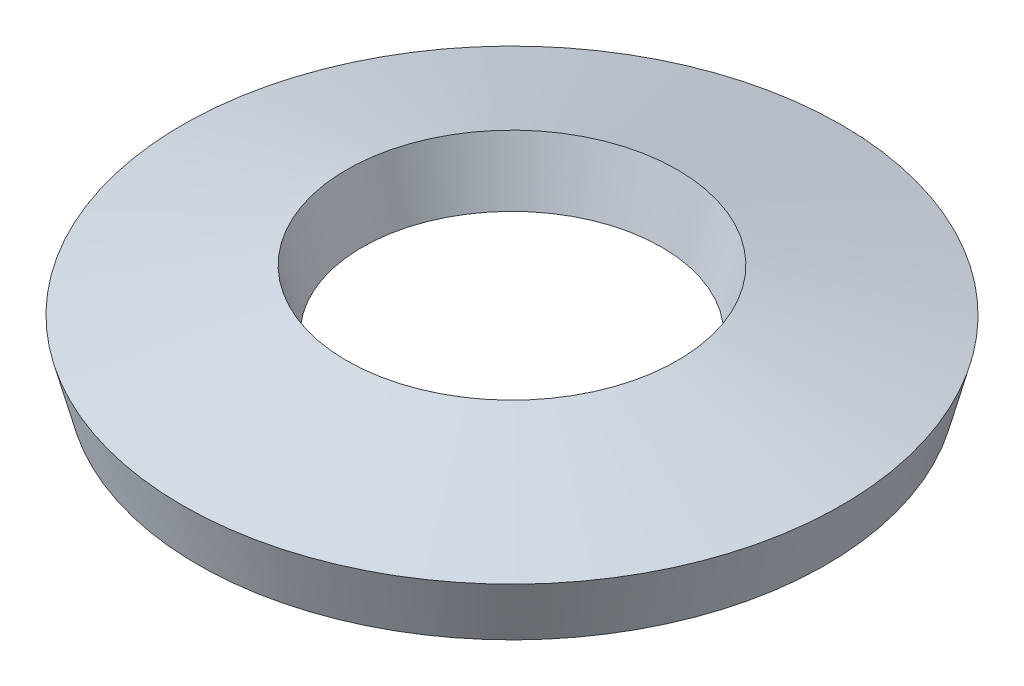
SolidWorks part; units mm, degrees
note: '?' marks a value the reader was unsure of.
ref_plane "Front" through (0, 0, 0) normal (0, 0, 1) x (1, 0, 0)
ref_plane "Top" through (0, 0, 0) normal (0, 1, 0) x (1, 0, 0)
ref_plane "Right" through (0, 0, 0) normal (1, 0, 0) x (0, 0, -1)
sketch "Sketch1" plane through (0, 0, 0) normal (0, 0, 1) x (1, 0, 0)
  line L0 (6.7625, 0) -> (3.2258, 0.9327)
  line L1 (3.2258, 0.9327) -> (3.5626, 2.2098)
  line L2 (3.5626, 2.2098) -> (7.0993, 1.2771)
  line L3 (7.0993, 1.2771) -> (6.7625, 0)
  line L4 (0, 0) -> (0, 2.2098) construction
  line L5 (-7.0993, 1.2771) -> (-6.7625, 0) construction
  line L6 (-3.5626, 2.2098) -> (-7.0993, 1.2771) construction
  line L7 (-3.2258, 0.9327) -> (-3.5626, 2.2098) construction
  line L8 (-6.7625, 0) -> (-3.2258, 0.9327) construction
  point P5 (3.3942, 1.5712)
  point P8 (-3.3942, 1.5712)
  dimension "ID" = 6.4516
  dimension "Thickness" = 1.3208
  dimension "D1" = 3.6576
revolve "Revolve1" add sketch "Sketch1" angle 360 about L4
sketch "Sketch15" plane through (0, 0, 0) normal (0, 1, 0) x (1, 0, 0)
  circle A0 centre (0, 0) radius 7.0993
  circle A1 centre (0, 0) radius 3.2258
ref_plane "Plane10" through (0, 2.2098, 0) normal (0, 1, 0) x (-1, 0, 0)
surface "Surface-Knit1"
surface "Surface-Extend1" parameters "D1"=1.27, "D2"=1.27
sketch "Sketch13" plane through (0, 2.2098, 0) normal (0, 1, 0) x (-1, 0, 0)
  line L0 (-7.277, 1.7321) -> (-2.8239, -0.3445)
  line L2 (-6.7625, 0) -> (-3.2258, 0) construction
  circle A3 centre (0, 0) radius 2.8448
  circle A4 centre (0, 0) radius 2.8448 construction
  circle A6 centre (0, 0) radius 7.4803
  circle A7 centre (0, 0) radius 7.4803 construction
  dimension "D1" = 25
  dimension "D2" = 0.381
  dimension "D3" = 0.381
extrude "Cut-Extrude-Thin12" [suppressed] cut sketch "Sketch13" against normal offset from surface (1.1996 mm away) 0.1651 thin
surface "Surface-Knit2"
surface "Surface-Extend2" parameters "D1"=0.762, "D2"=0.762
sketch "Sketch14" plane through (0, 0, 0) normal (0, 1, 0) x (1, 0, 0)
  line L0 (7.277, -1.7321) -> (2.8239, 0.3445) construction
  line L1 (7.277, -1.7321) -> (2.8239, 0.3445)
extrude "Cut-Extrude-Thin13" [suppressed] cut sketch "Sketch14" along normal offset from surface (0.1371 mm away) 0.1651 thin
chamfer "Chamfer1" [suppressed] distance 0.1486 angle 45
pattern_circular "CirPattern3" [suppressed] count 28 over 360
delete or keep bodies "Body-Delete1" type delete bodies bodies 120
delete or keep bodies "Body-Delete2" type delete bodies bodies 119
ref_plane "Contact Plane 1" through (0, 0, 0) normal (0, 1, 0) x (-1, 0, 0)
ref_plane "Contact Plane 2" through (0, 2.2098, 0) normal (0, 1, 0) x (-1, 0, 0)
ref_axis "Center Axis 1" through (0, 0, 0) along (0, 1, 0)?
equation "\"D1@Cut-Extrude-Thin12\" = \"Thickness@Sketch1\"*.125"
equation "\"D1@Cut-Extrude-Thin13\" = \"D1@Cut-Extrude-Thin12\""
equation "\"D1@Chamfer1\" = \"D1@Cut-Extrude-Thin12\"*.9"
